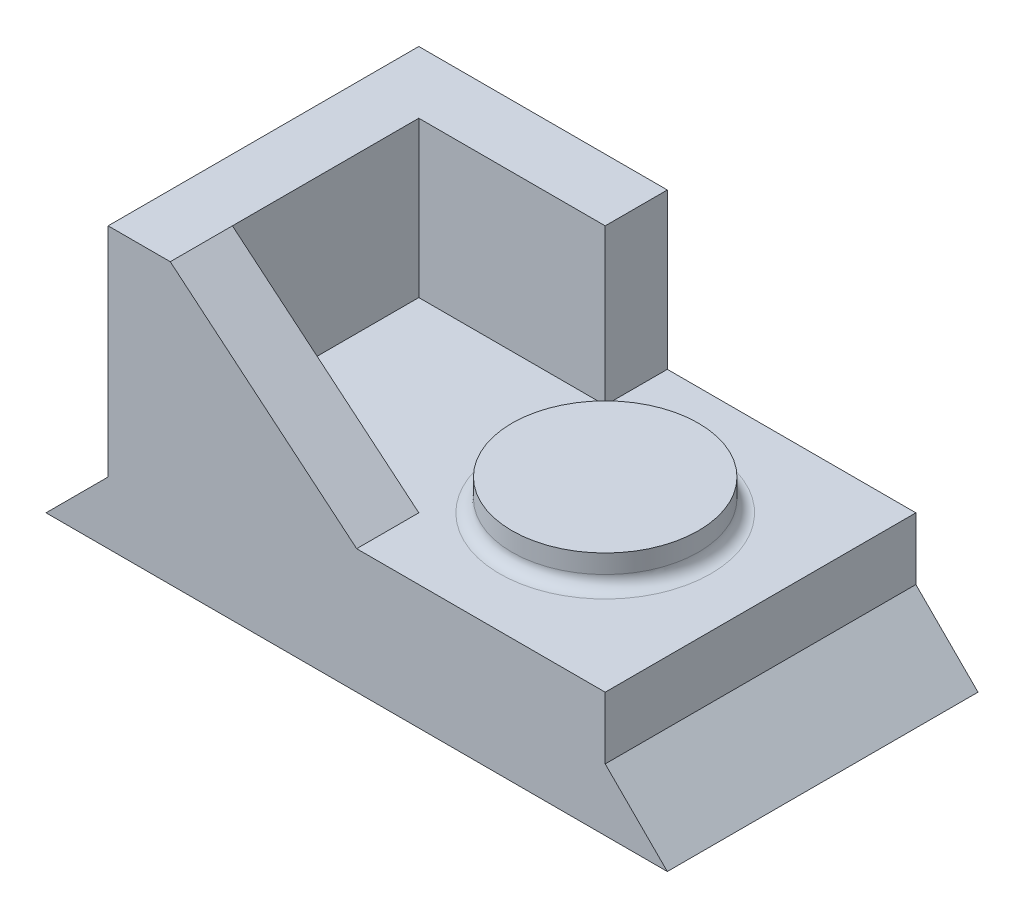
SolidWorks part; units mm, degrees
ref_plane "Front Plane" through (0, 0, 0) normal (0, 0, 1) x (1, 0, 0)
ref_plane "Top Plane" through (0, 0, 0) normal (0, 1, 0) x (1, 0, 0)
ref_plane "Right Plane" through (0, 0, 0) normal (1, 0, 0) x (0, 0, -1)
sketch "Esquisse1" plane through (0, 0, 0) normal (0, 0, 1) x (1, 0, 0)
  line L0 (0, 0) -> (100, 0)
  line L1 (100, 0) -> (90, 10)
  line L2 (90, 10) -> (90, 20)
  line L3 (90, 20) -> (50, 20)
  line L4 (50, 20) -> (50, 45)
  line L5 (50, 45) -> (10, 45)
  line L6 (10, 45) -> (10, 10)
  line L7 (10, 10) -> (0, 0)
  line L8 (50, 20) -> (20, 45)
  line L9 (50, 20) -> (10, 20)
  line L10 (20, 45) -> (20, 20)
  line L11 (65, 46.3345) -> (65, -26.9751) construction
  line L12 (80, 20) -> (80, 25)
  line L13 (80, 25) -> (65, 25)
  line L14 (65, 25) -> (65, 20)
  line L15 (65, 20) -> (80, 20)
  dimension "D1" = 100
  dimension "D2" = 10
  dimension "D3" = 10
  dimension "D4" = 10
  dimension "D5" = 25
  dimension "D6" = 15
  dimension "D7" = 5
  dimension "D8" = 15
  dimension "D9" = 30
  dimension "D10" = 10
  dimension "D11" = 10
  dimension "D12" = 25
extrude "Boss.-Extru.1" add sketch "Esquisse1" along normal mid plane 50 contours L11 L3 L9 L6 L7 L0 | L10 L5 L6 L9 | L3 L11 L0 L1 L2 region at (36.1594, 9.7101, 0) region at (78.9394, 9.3939, 0) region at (15, 32.5, 0)
extrude "Boss.-Extru.4" add sketch "Esquisse1<5>" along normal up to surface (25 mm away) from offset 15 contours L8 L10 L9 region at (30, 28.3333, 0) up to face at (42.5, 18.75, 25)
sketch "Esquisse1<5>" plane through (0, 0, 0) normal (0, 0, 1) x (1, 0, 0) same geometry as "Esquisse1"
extrude "Boss.-Extru.5" add sketch "Esquisse1<6>" against normal up to surface (25 mm away) from offset 15 contours L8 L10 L9 | L8 L4 L5 region at (30, 28.3333, 0) region at (40, 36.6667, 0) up to face at (42.5, 18.75, -25) offset against normal yes
sketch "Esquisse1<6>" plane through (0, 0, 0) normal (0, 0, 1) x (1, 0, 0) same geometry as "Esquisse1"
revolve "Révolution1" add sketch "Esquisse1<9>" angle 360 about L11 region at (72.5, 22.5, 0)
sketch "Esquisse1<9>" plane through (0, 0, 0) normal (0, 0, 1) x (1, 0, 0) same geometry as "Esquisse1"
fillet "Congé1" radius 2 1 edges at (80, 20, 0)
